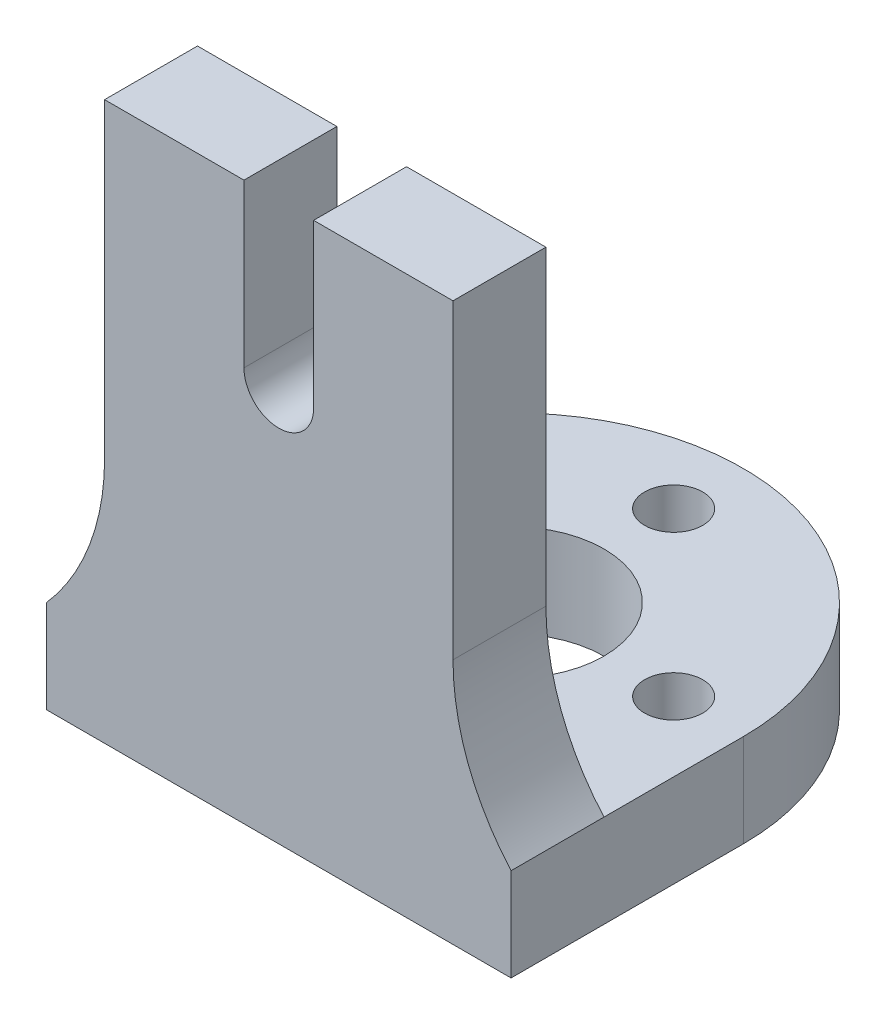
SolidWorks part; units mm, degrees
ref_plane "Спереди" through (0, 0, 0) normal (0, 0, 1) x (1, 0, 0)
ref_plane "Сверху" through (0, 0, 0) normal (0, 1, 0) x (1, 0, 0)
ref_plane "Справа" through (0, 0, 0) normal (1, 0, 0) x (0, 0, -1)
sketch "Sketch1" plane through (0, 0, 0) normal (0, 1, 0) x (1, 0, 0)
  line L0 (-10, 0) -> (-10, -10)
  line L1 (-10, -10) -> (10, -10)
  line L2 (10, -10) -> (10, 0)
  circle A0 centre (0, 0) radius 10
  dimension "D1" = 20
  dimension "D2" = 10
extrude "Boss-Extrude1" add sketch "Sketch1" along normal blind 4 contours A0 L0 L1 L2 | A0 | A0 L0 L1
sketch "Sketch3" plane through (0, 4, 0) normal (0, 1, 0) x (1, 0, 0)
  circle A0 centre (0, 0) radius 4
  circle A1 centre (0, 7) radius 1.25
  circle A2 centre (7, 0) radius 1.25
  circle A3 centre (0, -7) radius 1.25
  circle A4 centre (-7, 0) radius 1.25
  point P5 (0, 0)
  point P6 (6.7151, 0)
  point P14 (0, 0)
  dimension "D1" = 8
  dimension "D2" = 2.5
  dimension "D4" = 14
  dimension "D3" = 4
extrude "Cut-Extrude1" cut sketch "Sketch3" against normal blind 4
sketch "Sketch4" plane through (0, 4, 0) normal (0, 1, 0) x (1, 0, 0)
  line L1 (-10, -10) -> (10, -10)
  line L2 (-10, -10) -> (-10, -6)
  line L3 (-10, -6) -> (10, -6)
  line L4 (10, -10) -> (10, -6)
  line L5 (10, -10) -> (10, 0) construction
  dimension "D1" = 4
  dimension "D2" = 20
extrude "Boss-Extrude2" add sketch "Sketch4" along normal blind 20
sketch "Sketch5" plane through (0, 0, 6) normal (0, 0, -1) x (-1, 0, 0)
  line L0 (-1.5, 17) -> (-1.5, 24)
  line L1 (-10, 24) -> (10, 24) construction
  line L2 (-1.5, 24) -> (1.5, 24)
  line L3 (1.5, 24) -> (1.5, 17)
  circle A0 centre (0, 17) radius 1.5
  point P7 (0, 0)
  line M4 (10, 24) -> (-10, 24)
  dimension "D1" = 3
  dimension "D2" = 7
extrude "Cut-Extrude2" cut sketch "Sketch5" against normal blind 30 contours A0 L3 L0 M4 | A0
sketch "Sketch6" plane through (0, 0, 6) normal (0, 0, -1) x (-1, 0, 0)
  circle A0 centre (0, 17) radius 3.25
  dimension "D1" = 6.5
extrude "Cut-Extrude3" cut sketch "Sketch6" against normal blind 1
sketch "Sketch7" plane through (0, 0, 6) normal (0, 0, -1) x (-1, 0, 0)
  line L0 (7.5, 24) -> (7.5, 4)
  line L1 (1.5, 24) -> (10, 24) construction
  line L2 (-10, 4) -> (-0.75, 4) construction
  line L3 (0, 17) -> (0, 5.0387) construction
  line L4 (-7.5, 24) -> (-7.5, 4)
  line M4 (-1.5, 24) -> (-10, 24)
  line M5 (-10, 24) -> (-10, 4)
  line M6 (-10, 4) -> (-0.75, 4)
  line M7 (10, 4) -> (10, 24)
  line M8 (10, 24) -> (1.5, 24)
  dimension "D1" = 15
extrude "Cut-Extrude4" cut sketch "Sketch7" against normal blind 4 contours L0 M8 M6 M7 | L4 M4 M5 M6
fillet "Fillet1" radius 10 2 edges at (7.5, 4, 8) (-7.5, 4, 8)
